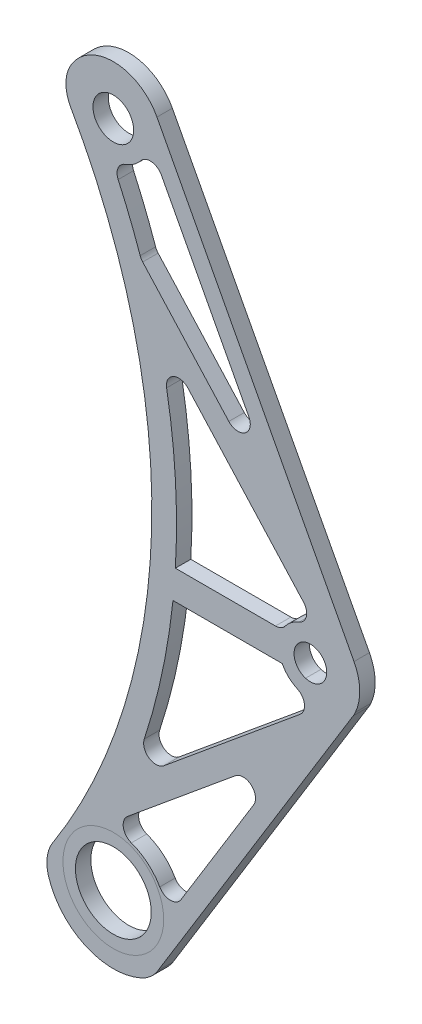
SolidWorks part; units mm, degrees
material "6061-T6 (SS)"
ref_plane "X-Y Datum" through (0, 0, 0) normal (0, 0, 1) x (1, 0, 0)
ref_plane "X-Z Datum" through (0, 0, 0) normal (0, 1, 0) x (1, 0, 0)
ref_plane "Y-Z Datum" through (0, 0, 0) normal (1, 0, 0) x (0, 0, -1)
sketch "Sketch1" plane through (0, 0, 0) normal (0, 0, 1) x (1, 0, 0)
  line L0 (0, 0) -> (0, 137.668) construction
  line L1 (0, 137.668) -> (40.5829, 60.8625) construction
  line L2 (40.5829, 60.8625) -> (0, 0) construction
  line L3 (-13.97, 0) -> (-10.16, 137.668)
  line L4 (8.9831, 142.4145) -> (49.566, 65.6091)
  line L5 (49.566, 56.116) -> (8.1778, -11.3263)
  circle A0 centre (0, 0) radius 7.8105
  circle A1 centre (40.5829, 60.8625) radius 3.3655
  circle A2 centre (0, 137.668) radius 4.191
  arc A3 (-10.16, 137.668) -> (8.9831, 142.4145) centre (0, 137.668) cw
  arc A4 (49.566, 65.6091) -> (49.566, 56.116) centre (40.5829, 60.8625) cw
  arc A5 (8.1778, -11.3263) -> (-13.97, 0) centre (0, 0) cw
  arc A6 (-10.16, 137.668) -> (-13.97, 0) centre (-120.8325, 71.8442) cw
  circle A7 centre (0, 0) radius 11.5718
  point P16 (50.7429, 60.8625)
  dimension "D4" = 15.621
  dimension "D5" = 6.731
  dimension "D6" = 8.382
  dimension "D7" = 13.97
  dimension "D8" = 10.16
  dimension "D9" = 10.16
  dimension "D1" = 137.668
  dimension "D2" = 86.868
  dimension "D3" = 73.152
  dimension "D11" = 125.83
extrude "Boss-Extrude1" add sketch "Sketch1" along normal blind 3.175 contours A3 A6 A5 L5 A4 L4 A2 A1 A0 | A6 A7 A0 region at (18.3815, 67.9714, 0) region at (-11.2445, 0, 0)
sketch "Sketch2" plane through (0, 0, 3.175) normal (0, 0, 1) x (1, 0, 0)
  line L0 (10.9735, 0.5136) -> (45.1141, 56.146)
  line L1 (49.566, 56.116) -> (8.1778, -11.3263) construction
  line L2 (45.4652, 65.2146) -> (7.3584, 137.334)
  line L3 (8.9831, 142.4145) -> (49.566, 65.6091) construction
  line L4 (34.771, 63.8625) -> (12.7772, 63.8625)
  line L5 (34.771, 57.8625) -> (12.2832, 57.8625)
  line L6 (42.7865, 67.0206) -> (9.0338, 104.248)
  line L7 (37.3415, 80.5892) -> (5.7001, 115.488)
  line L8 (45.1141, 56.146) -> (3.1725, 21.4652)
  line L9 (36.9014, 42.7633) -> (-1.6872, 10.8552)
  line L10 (40.5829, 60.8625) -> (-57.185, 60.8625)
  arc A4 (-0.4312, 130.3146) -> (-1.6872, 10.8552) centre (-120.8325, 71.8442) cw
  arc A5 (-13.97, 0) -> (-10.16, 137.668) centre (-120.8325, 71.8442) ccw construction
  circle A7 centre (0, 0) radius 10.9855
  circle A9 centre (40.5829, 60.8625) radius 6.5405
  circle A10 centre (0, 137.668) radius 7.366
  circle A11 centre (0, 137.668) radius 4.191 construction
  circle A12 centre (40.5829, 60.8625) radius 3.3655 construction
  circle A13 centre (0, 0) radius 7.8105 construction
  dimension "D3" = 3.175
  dimension "D1" = 3.175
  dimension "D2" = 3.175
  dimension "D6" = 5.08
  dimension "D4" = 3.81
  dimension "D5" = 3.81
  dimension "D7" = 5.08
  dimension "D8" = 5.08
  dimension "D9" = 3
  dimension "D10" = 3
extrude "Cut-Extrude1" cut sketch "Sketch2" against normal blind 6.35 contours A7 L0 L9 A4 | A9 A4 L8 | L6 A4 | A10 A4 L7 L2 region at (16.5204, 19.3286, 3.175) region at (20.5771, 45.529, 3.175) region at (15.0547, 113.2832, 3.175) region at (22.4636, 77.3864, 3.175)
fillet "Fillet1" radius 2.54 12 edges at (10.9735, 0.5136, 1.5875) (36.9014, 42.7633, 1.5875) (44.3643, 55.526, 1.5875) (3.1725, 21.4652, 1.5875) (9.0338, 104.248, 1.5875) (37.3415, 80.5892, 1.5875) (5.7001, 115.488, 1.5875) (-0.4312, 130.3146, 1.5875) (7.3584, 137.334, 1.5875) (-1.6872, 10.8552, 1.5875) (42.7865, 67.0206, 1.5875) (34.771, 63.8625, 1.5875)
sketch "Sketch3" [suppressed] plane through (0, 0, 4.7625) normal (0, 0, 1) x (1, 0, 0)
  line L1 (13.9694, 0.1347) -> (39.7508, 21.6818)
  line L2 (9.979, 66.6708) -> (39.902, 40.8139)
  line L3 (55.423, 60.7241) -> (9.3949, 172.5239) construction
  line L6 (12.9992, 5.1168) -> (35.8725, 24.2335)
  line L8 (8.1778, -11.3263) -> (55.423, 52.9883) construction
  arc A0 (39.902, 40.8139) -> (35.8725, 24.2335) centre (43.2483, 31.2208) ccw
  arc A1 (-1.655, 13.8716) -> (12.9992, 5.1168) centre (0, 0) cw
  arc A3 (0.9228, 58.462) -> (-1.655, 13.8716) centre (-31.1833, 37.9483) cw
  circle A4 centre (43.2483, 31.2208) radius 10.16
  circle A5 centre (0, 0) radius 13.97
  arc A6 (0.9228, 58.462) -> (9.979, 66.6708) centre (0, 68.58) ccw
  circle A7 centre (0, 68.58) radius 10.16
  arc A8 (-5.9452, 60.3411) -> (-7.4548, 11.8147) centre (-23.0858, 36.5876) cw
  arc A9 (-13.4408, 9.525) -> (-10.5128, 62.23) centre (-35.7711, 37.1994) ccw construction
  dimension "D1" = 10.16
  dimension "D2" = 10.16
  dimension "D3" = 13.97
  dimension "D6" = 6.7275
  dimension "D9" = 12.7
  dimension "D7" = 38.1
  dimension "D4" = 29.81
  dimension "D5" = 5.08
  dimension "D8" = 5.08
  dimension "D11" = 75.318
extrude "Cut-Extrude2" [suppressed] cut sketch "Sketch3" against normal blind 6.35 contours A6 A3 A1 L6 A0 L2 | A5 L1 A4 L6 | L6 A0 L2 A6 A3 A1
sketch3d "3DSketch1"
  line L0 (0, 137.668, 3.175) -> (0, 137.668, 0) construction
  line L1 (40.5829, 60.8625, 3.175) -> (40.5829, 60.8625, 0) construction
  point P0 (0, 137.668, 3.175)
  point P1 (40.5829, 60.8625, 3.175)
fillet "Fillet2" [suppressed] radius 6.35
fillet "Fillet4" [suppressed] radius 6.35
ref_axis "Axis1" through (0, 137.668, 3.175) along (0, 0, -1)
ref_axis "Axis2" through (40.5829, 60.8625, 3.175) along (0, 0, -1)
ref_plane "Plane1" through (23.5426, 4.1512, 0) normal (0.9848, 0.1736, 0) x (0, 0, -1)
ref_plane "Plane2" through (19.8415, -6.142, 0) normal (0.9553, -0.2957, 0) x (0, 0, -1)
sketch "Sketch4" plane through (23.5426, 4.1512, 0) normal (0.9848, 0.1736, 0) x (0, 0, -1)
  line L0 (-3.175, 166.0937) -> (-3.175, 170.2847)
sketch "Sketch5" plane through (19.8415, -6.142, 0) normal (0.9553, -0.2957, 0) x (0, 0, -1)
  line L0 (-3.175, 70.1413) -> (-3.175, 11.4039)
  line L1 (-0.3461, 48.6622) -> (-0.3461, 36.6839)
split line "Split Line1"
split line "Split Line2" [suppressed]
ref_point "Point2"
ref_axis "Axis3" through (0, 0, 3.175) along (0, 0, -1)
sketch "Sketch6" plane through (0, 0, 0) normal (0, 0, -1) x (-1, 0, 0)
  circle A0 centre (0, 0) radius 10.3708
split line "Split Line3"
fillet "Fillet5" radius 7.62 4 edges at (-13.97, 0, 1.5875) (-10.16, 137.668, 1.5875) (49.566, 56.116, 1.5875) (8.1778, -11.3263, 1.5875)
ref_point "Point4"
